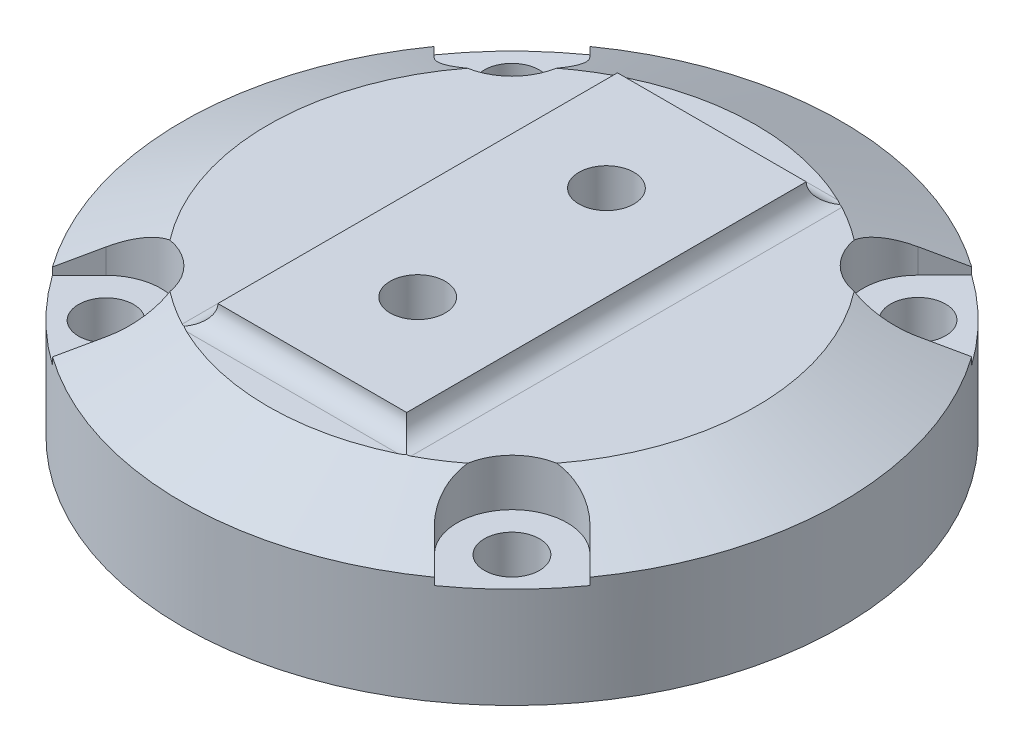
SolidWorks part; units mm, degrees
ref_plane "Front Plane" through (0, 0, 0) normal (0, 0, 1) x (1, 0, 0)
ref_plane "Top Plane" through (0, 0, 0) normal (0, 1, 0) x (1, 0, 0)
ref_plane "Right Plane" through (0, 0, 0) normal (1, 0, 0) x (0, 0, -1)
sketch "Sketch1" plane through (0, 0, 0) normal (0, 1, 0) x (1, 0, 0)
  circle A0 centre (0, 0) radius 20.955
  dimension "D1" = 41.91
extrude "Boss-Extrude1" add sketch "Sketch1" along normal blind 9.398
sketch "Sketch2" plane through (0, 9.398, 0) normal (0, 1, 0) x (1, 0, 0)
  line L1 (-6, 12.7) -> (6, 12.7)
  line L2 (-6, 12.7) -> (-6, -12.7)
  line L3 (-6, -12.7) -> (6, -12.7)
  line L4 (6, 12.7) -> (6, -12.7)
  point P4 (0, 12.7)
  point P6 (-6, 0)
  dimension "D1" = 25.4
  dimension "D2" = 12
extrude "Boss-Extrude2" add sketch "Sketch2" along normal blind 1.27
chamfer "Chamfer1" distance 2.54 angle 65 1 edges at (0, 9.398, 20.955) first distance on face at (0, 9.398, 20.955)
fillet "Fillet1" radius 1.27 4 edges at (0, 9.398, -12.7) (6, 9.398, 0) (0, 9.398, 12.7) (-6, 9.398, 0)
sketch "Sketch3" plane through (0, 10.668, 0) normal (0, 1, 0) x (1, 0, 0)
  circle A0 centre (0, 6) radius 1.75
  circle A1 centre (0, -6) radius 1.75
  dimension "D3" = 3.5
  dimension "D1" = 6
  dimension "D2" = 12
extrude "Cut-Extrude1" cut sketch "Sketch3" against normal up to next
sketch "Sketch4" plane through (0, 0, 0) normal (0, -1, 0) x (1, 0, 0)
  circle A0 centre (0, 0) radius 18.25 construction
  circle A1 centre (-12.9, 12.9094) radius 1.75
  circle A2 centre (12.9, 12.9094) radius 1.75
  circle A3 centre (12.8876, -12.9218) radius 1.75
  circle A4 centre (-12.9124, -12.897) radius 1.75
  dimension "D1" = 36.5
  dimension "D2" = 3.5
  dimension "D3" = 25.8
  dimension "D4" = 25.8064
  dimension "D5" = 25.8
extrude "Cut-Extrude2" cut sketch "Sketch4" against normal up to next
sketch "Sketch5" plane through (0, 9.398, 0) normal (0, 1, 0) x (1, 0, 0)
  line L0 (-15.3749, -10.4345) -> (-17.0802, -12.1399)
  line L1 (-12.9, -12.9094) -> (-10.5534, -10.5628) construction
  line L2 (-10.4251, -15.3843) -> (-12.1289, -17.0881)
  arc A4 (-10.4251, -15.3843) -> (-15.3749, -10.4345) centre (-12.9, -12.9094) ccw
  arc A5 (-17.0802, -12.1399) -> (-12.1289, -17.0881) centre (0, 0) ccw
  circle A6 centre (0, 0) radius 20.955 construction
  dimension "D1" = 3.5
extrude "Cut-Extrude3" cut sketch "Sketch5" against normal blind 3
pattern_circular "CirPattern2" count 4 over 360 about axis through (0, 6.858, 0) along (0, -1, 0) of "Cut-Extrude3"
